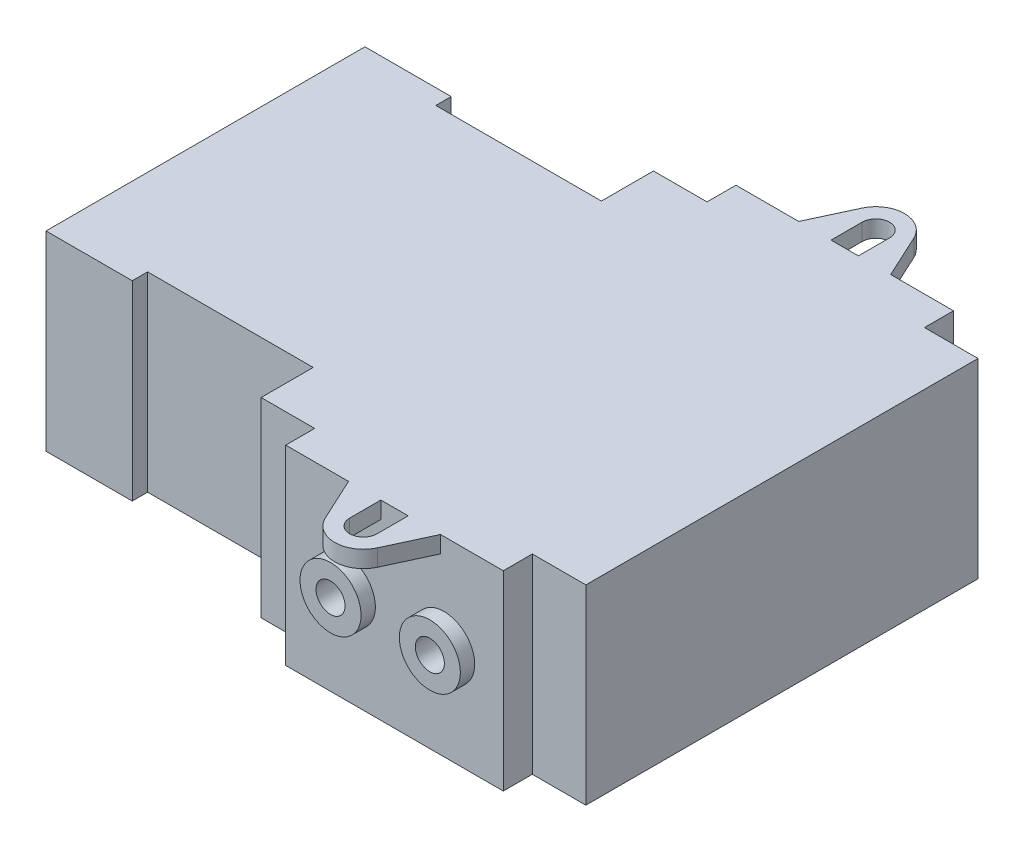
SolidWorks part; units mm, degrees
ref_plane "Front Plane" through (0, 0, 0) normal (0, 0, 1) x (1, 0, 0)
ref_plane "Top Plane" through (0, 0, 0) normal (0, 1, 0) x (1, 0, 0)
ref_plane "Right Plane" through (0, 0, 0) normal (1, 0, 0) x (0, 0, -1)
sketch "Sketch1" plane through (0, 0, 0) normal (0, 1, 0) x (1, 0, 0)
  line L0 (-34.798, 19.2532) -> (-24.384, 19.2532)
  line L1 (2.0701, 27.178) -> (28.3337, 27.178)
  line L2 (-34.798, 19.2532) -> (-34.798, -19.2532)
  line L3 (15.2019, 36.5172) -> (15.2019, 6.6677) construction
  line L4 (34.798, 23.6728) -> (34.798, -23.6728)
  line L5 (-34.2309, 27.0281) -> (35.0763, -27.6957) construction
  line L6 (-34.798, -27.178) -> (34.798, 27.178) construction
  line L7 (-24.384, 19.2532) -> (-24.384, 17.399)
  line L8 (-24.384, 17.399) -> (-4.3942, 17.399)
  line L9 (-4.3942, 17.399) -> (-4.3942, 23.6847)
  line L10 (0, 0) -> (-64.5877, 0) construction
  line L11 (0, 0) -> (50.5641, 0) construction
  line L12 (2.0701, 27.178) -> (2.0701, 23.6847)
  line L13 (2.0701, 23.6847) -> (-4.3942, 23.6847)
  line L14 (28.3337, 27.178) -> (28.3337, 23.6728)
  line L15 (28.3337, 23.6728) -> (34.798, 23.6728)
  line L16 (28.3337, -23.6728) -> (34.798, -23.6728)
  line L17 (28.3337, -27.178) -> (28.3337, -23.6728)
  line L18 (2.0701, -27.178) -> (28.3337, -27.178)
  line L19 (2.0701, -27.178) -> (2.0701, -23.6847)
  line L20 (2.0701, -23.6847) -> (-4.3942, -23.6847)
  line L21 (-4.3942, -17.399) -> (-4.3942, -23.6847)
  line L22 (-24.384, -17.399) -> (-4.3942, -17.399)
  line L23 (-34.798, -19.2532) -> (-24.384, -19.2532)
  line L24 (-24.384, -17.399) -> (-24.384, -19.2532)
  point P0 (0, 0)
  point P23 (34.798, 0)
  point P33 (-34.798, 0)
  dimension "D1" = 69.596
  dimension "D2" = 27.178
  dimension "D3" = 10.414
  dimension "D4" = 39.1922
  dimension "D5" = 9.779
  dimension "D6" = 1.8542
  dimension "D7" = 13.1318
  dimension "D8" = 13.1318
  dimension "D9" = 19.5961
  dimension "D10" = 3.5052
extrude "Boss-Extrude1" add sketch "Sketch1" along normal blind 23.0378
sketch "Sketch2" plane through (0, 0, 27.178) normal (0, 0, 1) x (1, 0, 0)
  line L0 (15.2019, 23.0378) -> (15.2019, -4.46) construction
  line L1 (2.0701, 23.0378) -> (28.3337, 23.0378) construction
  circle A0 centre (21.1963, 11.5189) radius 3.683
  circle A1 centre (9.2075, 11.5189) radius 3.683
  dimension "D1" = 7.366
  dimension "D2" = 7.366
  dimension "D3" = 5.9944
  dimension "D4" = 5.9944
  dimension "D5" = 11.5189
extrude "Boss-Extrude2" add sketch "Sketch2" along normal blind 1.7272
mirror "Mirror1" about plane through (0, 0, 0) normal (0, 0, 1) of "Boss-Extrude2"
sketch "Sketch3" plane through (0, 0, 28.9052) normal (0, 0, 1) x (1, 0, 0)
  circle A0 centre (21.1963, 11.5189) radius 1.7526
  circle A1 centre (9.2075, 11.5189) radius 1.7526
  dimension "D1" = 3.5052
  dimension "D2" = 3.5052
extrude "Cut-Extrude1" cut sketch "Sketch3" against normal through all
sketch "Sketch4" plane through (0, 23.0378, 0) normal (0, 1, 0) x (1, 0, 0)
  line L0 (15.2019, -33.1206) -> (15.2019, 43.2988) construction
  line L1 (9.652, -27.178) -> (12.0678, -32.3899)
  line L2 (2.0701, -27.178) -> (28.3337, -27.178) construction
  line L3 (20.7518, -27.178) -> (18.336, -32.3899)
  line L4 (15.2019, -39.1514) -> (14.9858, -39.6177)
  line L5 (40.7981, 0) -> (-39.0177, 0) construction
  line L6 (28.3337, -27.178) -> (28.3337, -23.6728) construction
  line L7 (15.2019, -39.1514) -> (15.504, -39.8033)
  line L8 (13.5509, -30.9372) -> (13.5509, -27.178)
  line L9 (16.8529, -30.9372) -> (16.8529, -27.178)
  line L10 (16.8529, -27.178) -> (20.7518, -27.178)
  line L11 (13.5509, -27.178) -> (9.652, -27.178)
  line L12 (16.8529, 27.178) -> (20.7518, 27.178)
  line L13 (13.5509, 27.178) -> (9.652, 27.178)
  line L14 (13.5509, 30.9372) -> (13.5509, 27.178)
  line L15 (16.8529, 30.9372) -> (16.8529, 27.178)
  line L16 (20.7518, 27.178) -> (18.336, 32.3899)
  line L17 (9.652, 27.178) -> (12.0678, 32.3899)
  arc A0 (12.0678, -32.3899) -> (18.336, -32.3899) centre (15.2019, -30.9372) ccw
  arc A1 (13.5509, -30.9372) -> (16.8529, -30.9372) centre (15.2019, -30.9372) ccw
  arc A2 (13.5509, 30.9372) -> (16.8529, 30.9372) centre (15.2019, 30.9372) cw
  arc A3 (12.0678, 32.3899) -> (18.336, 32.3899) centre (15.2019, 30.9372) cw
  line M8 (2.0701, -27.178) -> (28.3337, -27.178)
  line M14 (28.3337, 27.178) -> (2.0701, 27.178)
  dimension "D1" = 6.9088
  dimension "D2" = 3.302
  dimension "D3" = 30.9372
  dimension "D4" = 13.1318
  dimension "D5" = 5.5499
  dimension "D6" = 5.5499
extrude "Boss-Extrude3" add sketch "Sketch4" against normal blind 2.032 contours A1 L8 L1 A0 L3 L9 M8 | A3 L17 L14 A2 L15 L16 M14 region at (11.6014, 23.0378, 27.3104) region at (16.9853, 23.0378, -29.0576)
